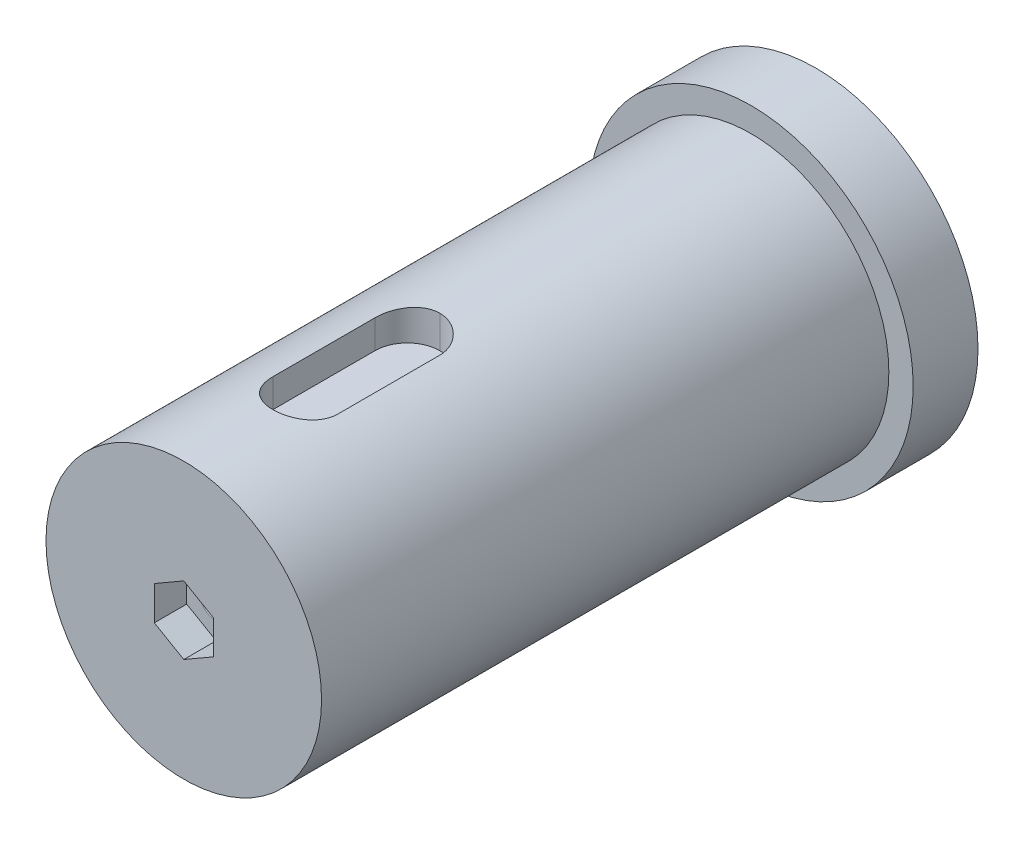
SolidWorks part; units mm, degrees
ref_plane "前视基准面" through (0, 0, 0) normal (0, 0, 1) x (1, 0, 0)
ref_plane "上视基准面" through (0, 0, 0) normal (0, 1, 0) x (1, 0, 0)
ref_plane "右视基准面" through (0, 0, 0) normal (1, 0, 0) x (0, 0, -1)
sketch "草图1" plane through (0, 0, 0) normal (0, 0, 1) x (1, 0, 0)
  circle A0 centre (0, 0) radius 8.5
  dimension "D1" = 17
extrude "凸台-拉伸1" add sketch "草图1" along normal blind 35
sketch "草图3" plane through (0, 0, 35) normal (0, 0, 1) x (1, 0, 0)
  line L1 (-2, 10.5) -> (2, 10.5)
  line L2 (-2, 10.5) -> (-2, 6.5)
  line L3 (-2, 6.5) -> (2, 6.5)
  line L4 (2, 10.5) -> (2, 6.5)
  line L5 (-2, 10.5) -> (2, 6.5) construction
  line L6 (-2, 6.5) -> (2, 10.5) construction
  circle A0 centre (0, 0) radius 8.5 construction
  point P0 (0, 8.5)
  dimension "D1" = 4
  dimension "D2" = 4
extrude "切除-拉伸1" cut sketch "草图3" against normal blind 14
sketch "草图4" plane through (0, 6.5, 0) normal (0, 1, 0) x (1, 0, 0)
  line L0 (-2, -21) -> (2, -21) construction
  line L1 (-2, -23) -> (-2, -21)
  line L2 (-2, -21) -> (0, -21)
  line L3 (0, -21) -> (2, -21)
  line L4 (2, -21) -> (2, -23)
  arc A1 (2, -23) -> (-2, -23) centre (0, -23) ccw
  line M3 (2, -35) -> (2, -21)
  line M4 (2, -21) -> (-2, -21)
  line M5 (-2, -21) -> (-2, -35)
  dimension "D1" = 2
extrude "凸台-拉伸2" add sketch "草图4" along normal up to surface (1.7614 mm away) contours A1 M3 M4 | A1 M4 M5 | L1 L2 L3 L4 A1 region at (1.5533, 6.5, 21.4467) region at (-1.5533, 6.5, 21.4467) up to face at (0, 4.1307, 28)
sketch "草图5" plane through (0, 6.5, 0) normal (0, 1, 0) x (1, 0, 0)
  line L0 (-2, -35) -> (2, -35) construction
  line L1 (-2, -29) -> (-2, -35)
  line L2 (-2, -35) -> (2, -35)
  line L3 (2, -35) -> (2, -29)
  arc A0 (-2, -29) -> (2, -29) centre (0, -29) ccw
  dimension "D1" = 6
extrude "凸台-拉伸3" add sketch "草图5" along normal up to surface (1.7614 mm away) up to face at (0, 4.1307, 28.5)
sketch "草图6" plane through (0, 0, 0) normal (0, 0, -1) x (-1, 0, 0)
  circle A0 centre (0, 0) radius 8.5 construction
  circle A1 centre (0, 0) radius 8.5
  circle A3 centre (0, 0) radius 10
  dimension "D1" = 1.5
extrude "凸台-拉伸4" add sketch "草图6" against normal blind 7
sketch "草图7" plane through (0, 0, 35) normal (0, 0, 1) x (1, 0, 0)
  circle A1 centre (0, 0) radius 8.5
  circle A2 centre (0, 0) radius 8.5
  dimension "D1" = 0
extrude "凸台-拉伸5" add sketch "草图7" along normal blind 3
ref_plane "基准面1" through (0, 0, 22.15) normal (0, 0, 1) x (1, 0, 0)
sketch "草图8" plane through (0, 6.5, 0) normal (0, 1, 0) x (1, 0, 0)
  line L0 (-2, -23) -> (-2, -23.2)
  line L1 (-2, -23) -> (-2, -29) construction
  line L2 (2, -23) -> (2, -23.2)
  line L3 (2, -23) -> (2, -29) construction
  line L4 (-2, -23.2) -> (2, -23.2)
  arc A0 (2, -23) -> (-2, -23) centre (0, -23) ccw
  dimension "D1" = 0.2
  dimension "D2" = 0.2
extrude "凸台-拉伸6" add sketch "草图8" along normal up to surface (1.7614 mm away) up to face at (0.0513, 8.3801, 25.9974)
sketch "草图9" plane through (0, 6.5, 0) normal (0, 1, 0) x (1, 0, 0)
  line L0 (-2, -29) -> (-2, -29.5)
  line L1 (2, -29) -> (2, -29.5)
  line L2 (-2, -29.5) -> (2, -29.5) construction
  line L3 (0, -29.5) -> (0, -31.5) construction
  line L4 (2, -29.5) -> (2, -31.5)
  line L5 (-2, -29.5) -> (-2, -31.5)
  line L6 (-2, -29) -> (2, -29)
  arc A1 (-2, -31.5) -> (2, -31.5) centre (0, -31.5) ccw
  dimension "D1" = 0.5
  dimension "D2" = 0.5
  dimension "D3" = 2
extrude "切除-拉伸2" cut sketch "草图9" along normal through all
fillet "圆角1" radius 2 2 edges at (-2, 7.3807, 23.2) (2, 7.3807, 23.2)
sketch "草图10" plane through (0, 0, 7) normal (0, 0, 1) x (1, 0, 0)
  circle A0 centre (0, 0) radius 8.5
  circle A1 centre (0, 0) radius 10
extrude "切除-拉伸3" cut sketch "草图10" against normal blind 3
sketch "草图11" plane through (0, 0, 38) normal (0, 0, 1) x (1, 0, 0)
  circle A0 centre (0, 0) radius 8.5
extrude "凸台-拉伸7" add sketch "草图11" along normal blind 1
sketch "草图12" plane through (0, 0, 39) normal (0, 0, 1) x (1, 0, 0)
  circle A0 centre (0, 0) radius 1
  dimension "D1" = 2
extrude "切除-拉伸4" cut sketch "草图12" against normal blind 5
sketch "草图13" plane through (0, 0, 39) normal (0, 0, 1) x (1, 0, 0)
  line L1 (0, 2.1) -> (-1.8187, 1.05)
  line L2 (-1.8187, 1.05) -> (-1.8187, -1.05)
  line L3 (-1.8187, -1.05) -> (0, -2.1)
  line L4 (0, -2.1) -> (1.8187, -1.05)
  line L5 (1.8187, -1.05) -> (1.8187, 1.05)
  line L6 (1.8187, 1.05) -> (0, 2.1)
  circle A0 centre (0, 0) radius 1.8187 construction
  dimension "D1" = 2.1
extrude "切除-拉伸5" cut sketch "草图13" against normal blind 2
sketch "草图14" plane through (0, 0, 34) normal (0, 0, 1) x (1, 0, 0)
  circle A0 centre (0, 0) radius 1
  circle A1 centre (0, 0) radius 0.85
  dimension "D1" = 1.7
extrude "凸台-拉伸8" add sketch "草图14" along normal up to surface (3 mm away) up to face at (0, 0, 37)
fillet "圆角2" radius 0.2 1 edges at (0.85, 0, 37)
sketch "草图15" plane through (0, 0, 0) normal (0, 0, -1) x (-1, 0, 0)
  line L1 (4, -4) -> (-4, -4)
  line L2 (4, -4) -> (4, 4)
  line L3 (4, 4) -> (-4, 4)
  line L4 (-4, -4) -> (-4, 4)
  line L5 (4, -4) -> (-4, 4) construction
  line L6 (4, 4) -> (-4, -4) construction
  point P0 (0, 0)
  dimension "D1" = 8
  dimension "D2" = 8
extrude "切除-拉伸6" cut sketch "草图15" against normal blind 6
